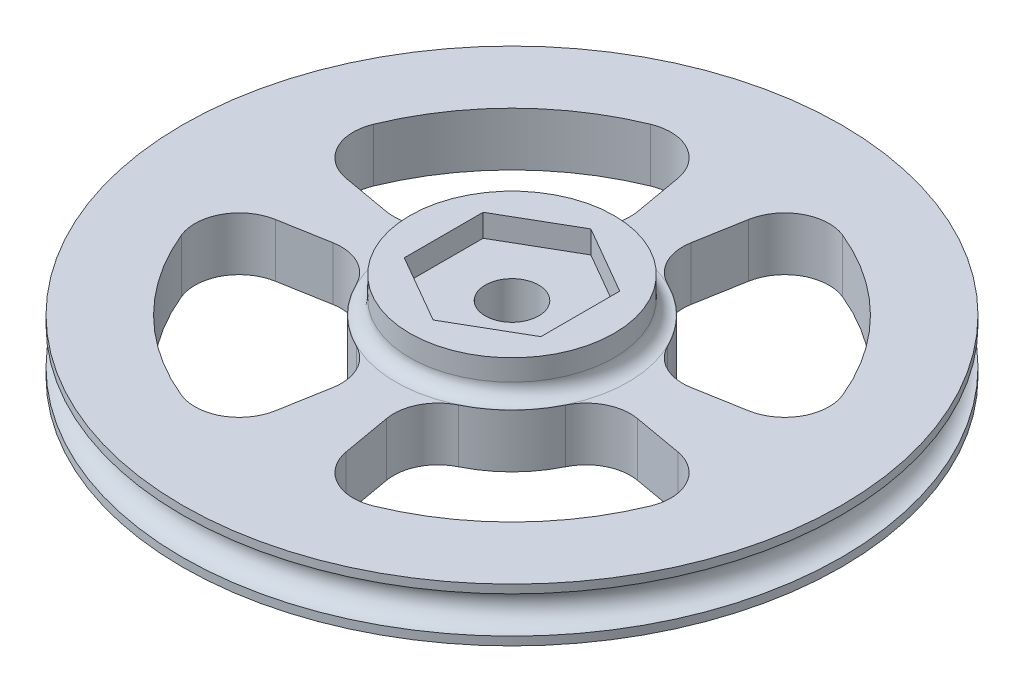
SolidWorks part; units mm, degrees
ref_plane "Front Plane" through (0, 0, 0) normal (0, 0, 1) x (1, 0, 0)
ref_plane "Top Plane" through (0, 0, 0) normal (0, 1, 0) x (1, 0, 0)
ref_plane "Right Plane" through (0, 0, 0) normal (1, 0, 0) x (0, 0, -1)
sketch "Sketch1" plane through (0, 0, 0) normal (1, 0, 0) x (0, 0, -1)
  line L0 (0, 1.651) -> (-29.718, 1.651) construction
  line L1 (-29.718, -1.651) -> (0, -1.651) construction
  line L2 (0, -1.651) -> (0, 1.651)
  line L3 (-29.718, 2.413) -> (0, 2.413)
  line L4 (-29.718, 0) -> (0, 0) construction
  line L5 (-29.718, 1.651) -> (-29.718, 2.413)
  line L6 (0, 2.413) -> (0, 1.651)
  line L7 (0, -2.413) -> (0, -1.651)
  line L8 (-29.718, -1.651) -> (-29.718, -2.413)
  line L9 (-29.718, -2.413) -> (0, -2.413)
  arc A0 (-29.718, 1.651) -> (-29.718, -1.651) centre (-29.718, 0) cw
  point P4 (0, 0)
  dimension "D1" = 29.718
  dimension "D2" = 3.302
  dimension "D3" = 0.762
revolve "Revolve1" add sketch "Sketch1" angle 360 about L2
ref_axis "Axis1" through (0, 2.413, 0) along (0, -1, 0)
sketch "Sketch4" plane through (0, 2.413, 0) normal (0, 1, 0) x (1, 0, 0)
  line L0 (-22.5127, -3.9696) -> (0, 0) construction
  line L1 (-18.1509, -3.2005) -> (-13.7256, -2.4202)
  line L2 (-2.4202, -13.7256) -> (-3.2005, -18.1509)
  line L3 (0, 0) -> (-3.9696, -22.5127) construction
  line L4 (0, 0) -> (-22.1873, 0) construction
  arc A0 (-21.1586, -8.654) -> (-8.654, -21.1586) centre (0, 0) ccw
  arc A1 (-9.4363, -4.6051) -> (-4.6051, -9.4363) centre (0, 0) ccw
  arc A2 (-4.6051, -9.4363) -> (-2.4202, -13.7256) centre (-6.3594, -13.031) cw
  arc A3 (-13.7256, -2.4202) -> (-9.4363, -4.6051) centre (-13.031, -6.3594) cw
  arc A4 (-21.1586, -8.654) -> (-18.1509, -3.2005) centre (-17.4563, -7.1397) cw
  arc A5 (-8.654, -21.1586) -> (-3.2005, -18.1509) centre (-7.1397, -17.4563) ccw
  point P8 (-1.8233, -10.3405)
  point P11 (-10.3405, -1.8233)
  dimension "D2" = 10.5
  dimension "D4" = 4
  dimension "D5" = 4
  dimension "D6" = 4
  dimension "D7" = 4
  dimension "D1" = 70
  dimension "D3" = 22.86
  dimension "D8" = 10
extrude "Cut-Extrude1" cut sketch "Sketch4" against normal through all
pattern_circular "CirPattern1" count 4 over 360 about axis through (0, 2.413, 0) along (0, -1, 0) of "Cut-Extrude1"
sketch "Sketch8" plane through (0, 2.413, 0) normal (0, 1, 0) x (1, 0, 0)
  circle A0 centre (0, 0) radius 9.2075
  dimension "D1" = 18.415
extrude "Boss-Extrude1" add sketch "Sketch8" along normal blind 3.175
sketch "Sketch6" plane through (0, 5.588, 0) normal (0, 1, 0) x (1, 0, 0)
  line L0 (0, 0) -> (0, 7.1124) construction
  line L1 (0, 7.1124) -> (-6.1595, 3.5562)
  line L2 (-6.1595, 3.5562) -> (-6.1595, -3.5562)
  line L3 (-6.1595, -3.5562) -> (0, -7.1124)
  line L4 (0, -7.1124) -> (6.1595, -3.5562)
  line L5 (6.1595, -3.5562) -> (6.1595, 3.5562)
  line L6 (6.1595, 3.5562) -> (0, 7.1124)
  circle A0 centre (0, 0) radius 6.1595 construction
  dimension "D1" = 12.319
extrude "Cut-Extrude2" cut sketch "Sketch6" against normal blind 2.032
sketch "Sketch7" plane through (0, 5.588, 0) normal (0, 1, 0) x (1, 0, 0)
  circle A0 centre (0, 0) radius 2.413
  dimension "D1" = 4.826
extrude "Cut-Extrude3" cut sketch "Sketch7" against normal through all
fillet "Fillet1" radius 1.27 1 edges at (0, 2.413, -9.2075)
